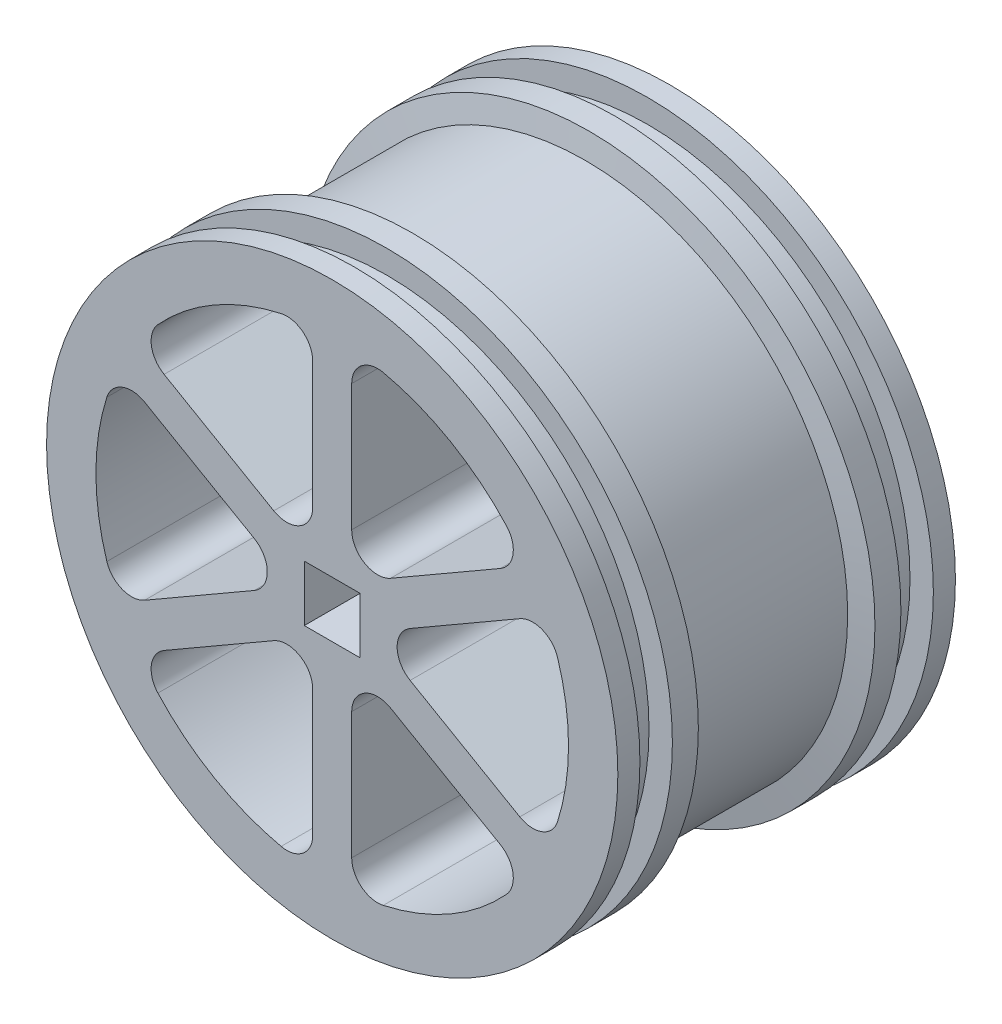
SolidWorks part; units mm, degrees
ref_plane "Front Plane" through (0, 0, 0) normal (0, 0, 1) x (1, 0, 0)
ref_plane "Top Plane" through (0, 0, 0) normal (0, 1, 0) x (1, 0, 0)
ref_plane "Right Plane" through (0, 0, 0) normal (1, 0, 0) x (0, 0, -1)
sketch "Sketch1" plane through (0, 0, 0) normal (1, 0, 0) x (0, 0, -1)
  line L1 (0, 22) -> (1.7, 22)
  line L2 (1.7, 22) -> (1.7, 20.2)
  line L3 (1.7, 20.2) -> (4.2, 20.2)
  line L4 (4.2, 20.2) -> (4.2, 22)
  line L5 (4.2, 22) -> (6.2, 22)
  line L6 (6.2, 22) -> (6.5, 20.2)
  line L7 (19.8, 22) -> (19.5, 20.2)
  line L8 (19.5, 20.2) -> (6.5, 20.2)
  line L10 (0, 18.2) -> (26, 18.2)
  line L11 (19.8, 22) -> (21.8, 22)
  line L12 (21.8, 22) -> (21.8, 20.2)
  line L13 (21.8, 20.2) -> (24.3, 20.2)
  line L14 (24.3, 20.2) -> (24.3, 22)
  line L15 (24.3, 22) -> (26, 22)
  line L18 (-0.3222, 0) -> (27.2819, 0) construction
  line L19 (0, 0) -> (0, 18.2) construction
  line L20 (0, 22) -> (0, 1028.7814) construction
  line L21 (0, 22) -> (0, 18.2)
  line L22 (26, 22) -> (26, 18.2)
  dimension "D1" = 22
  dimension "D2" = 1.7
  dimension "D3" = 2
  dimension "D4" = 0.3
  dimension "D5" = 2.3
  dimension "D6" = 3.8
  dimension "D7" = 1.8
  dimension "D8" = 2.5
  dimension "D9" = 26
revolve "Revolve1" add sketch "Sketch1" angle 360 about L18
sketch "Sketch2" plane through (0, 0, 0) normal (0, 0, 1) x (1, 0, 0)
  line L0 (0, 0) -> (0, 18.2) construction
  line L1 (-1.5, 18.2) -> (-1.5, 0)
  line L2 (-1.5, 18.2) -> (1.5, 18.2)
  line L3 (-1.5, 0) -> (1.5, 0)
  line L4 (1.5, 18.2) -> (1.5, 0)
  line L5 (-1.5, 18.2) -> (1.5, 0) construction
  line L6 (-1.5, 0) -> (1.5, 18.2) construction
  circle A0 centre (0, 0) radius 18.2 construction
  point P6 (0, 9.1)
  dimension "D1" = 18.2
  dimension "D2" = 3
extrude "Boss-Extrude1" add sketch "Sketch2" against normal blind 24
pattern_circular "CirPattern1" count 6 over 360 about axis through (0, 0, 0.3222) along (0, 0, 1) of "Boss-Extrude1" reverse direction yes
sketch "Sketch3" plane through (0, 0, 0) normal (0, 0, 1) x (1, 0, 0)
  line L1 (-2.15, -2.15) -> (2.15, -2.15)
  line L2 (-2.15, -2.15) -> (-2.15, 2.15)
  line L3 (-2.15, 2.15) -> (2.15, 2.15)
  line L4 (2.15, -2.15) -> (2.15, 2.15)
  line L5 (-2.15, -2.15) -> (2.15, 2.15) construction
  line L6 (-2.15, 2.15) -> (2.15, -2.15) construction
  point P0 (0, 0)
  dimension "D1" = 4.3
extrude "Cut-Extrude1" cut sketch "Sketch3" against normal through all both and the other way through all
fillet "Fillet1" radius 2 18 edges at (-14.958, 10.3681, -12) (16.458, -7.77, -12) (-1.5, 18.1381, -12) (-1.5, 2.5981, -12) (1.5, 18.1381, -12) (14.958, 10.3681, -12) (1.5, 2.5981, -12) (16.458, 7.77, -12) (3, 0, -12) (1.5, -2.5981, -12) (14.958, -10.3681, -12) (1.5, -18.1381, -12) (-1.5, -2.5981, -12) (-1.5, -18.1381, -12) (-14.958, -10.3681, -12) (-16.458, -7.77, -12) (-16.458, 7.77, -12) (-3, 0, -12)
fillet "Fillet2" radius 2 1 edges at (18.2, 0, -26)
